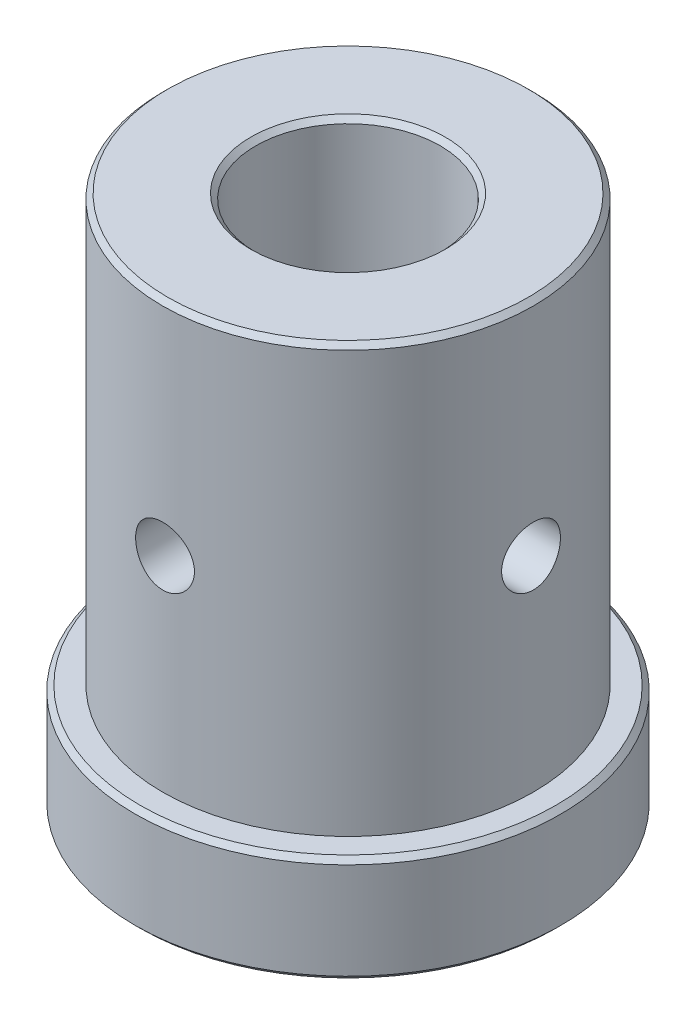
SolidWorks part; units mm, degrees
material "Nylon 101"
ref_plane "Front Plane" through (0, 0, 0) normal (0, 0, 1) x (1, 0, 0)
ref_plane "Top Plane" through (0, 0, 0) normal (0, 1, 0) x (1, 0, 0)
ref_plane "Right Plane" through (0, 0, 0) normal (1, 0, 0) x (0, 0, -1)
sketch "Sketch1" plane through (0, 0, 0) normal (0, 1, 0) x (1, 0, 0)
  circle A0 centre (0, 0) radius 11.049
  dimension "D1" = 22.098
extrude "Boss-Extrude1" add sketch "Sketch1" along normal blind 25.4
sketch "Sketch2" plane through (0, 0, 0) normal (0, -1, 0) x (1, 0, 0)
  circle A0 centre (0, 0) radius 12.7
  dimension "D1" = 25.4
extrude "Boss-Extrude2" add sketch "Sketch2" along normal blind 6.35
sketch "Sketch5" plane through (0, -6.35, 0) normal (0, -1, 0) x (1, 0, 0)
  circle A0 centre (0, 0) radius 11.176
  dimension "D1" = 22.352
extrude "Cut-Extrude2" cut sketch "Sketch5" against normal blind 5.5453
sketch "Sketch6" plane through (0, -0.8047, 0) normal (0, -1, 0) x (1, 0, 0)
  circle A0 centre (0, 0) radius 7.2746
  dimension "D1" = 14.5491
extrude "Cut-Extrude3" cut sketch "Sketch6" against normal blind 0.2
ref_plane "Plane2" through (0, 9.525, 0) normal (0, -1, 0) x (-1, 0, 0)
sketch "Sketch3" plane through (0, -6.35, 0) normal (0, -1, 0) x (1, 0, 0)
  circle A0 centre (0, 0) radius 5.5
  dimension "D1" = 11
extrude "Cut-Extrude1" cut sketch "Sketch3" against normal through all
sketch "Sketch4" plane through (0, -6.35, 0) normal (0, -1, 0) x (1, 0, 0)
  circle A0 centre (0, 0) radius 11.1125
  dimension "D1" = 22.225
chamfer "Chamfer1" distance 0.3 angle 45 6 edges at (0, 0, -12.7) (0, -6.35, -12.7) (0, 25.4, 11.049) (0, 25.4, -5.5) (0, -0.6047, -5.5) (0, -6.35, -11.176)
sketch "Sketch7" plane through (0, 0, 0) normal (0, 0, 1) x (1, 0, 0)
  line L0 (12.4, 0) -> (-12.4, 0) construction
  circle A0 centre (0, 12.192) radius 1.7526
  point P4 (0, 0)
  dimension "D1" = 3.5052
  dimension "D2" = 12.192
extrude "Cut-Extrude4" cut sketch "Sketch7" against normal through all both and the other way through all
sketch "Sketch8" plane through (0, 0, 0) normal (1, 0, 0) x (0, 0, -1)
  line L0 (12.4, 0) -> (-12.4, 0) construction
  circle A0 centre (0, 12.192) radius 1.7526
  point P2 (0, 0)
  dimension "D1" = 3.5052
  dimension "D2" = 12.192
extrude "Cut-Extrude5" cut sketch "Sketch8" against normal through all both and the other way through all
equation "\"D1@Chamfer1\"=.3mm"
